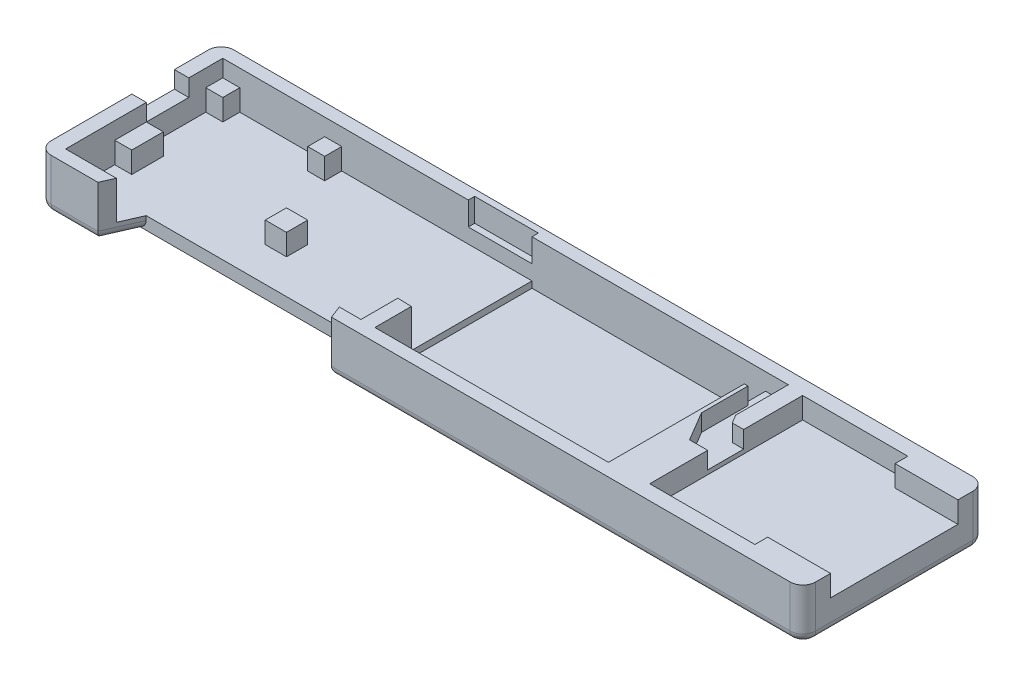
SolidWorks part; units mm, degrees
ref_plane "前视基准面" through (0, 0, 0) normal (0, 0, 1) x (1, 0, 0)
ref_plane "上视基准面" through (0, 0, 0) normal (0, 1, 0) x (1, 0, 0)
ref_plane "右视基准面" through (0, 0, 0) normal (1, 0, 0) x (0, 0, -1)
sketch "草图3" plane through (0, 0, 0) normal (0, 1, 0) x (1, 0, 0)
  line L1 (-39.9314, 29.2531) -> (140.0686, 29.2531)
  line L2 (-39.9314, 29.2531) -> (-39.9314, -13.7469)
  line L3 (-39.9314, -13.7469) -> (140.0686, -13.7469)
  line L4 (140.0686, 29.2531) -> (140.0686, -13.7469)
extrude "凸台-拉伸1" add sketch "草图3" along normal blind 12
sketch "草图4" plane through (0, 0, 0) normal (0, 1, 0) x (1, 0, 0)
  line L0 (-22.4696, -5.8589) -> (26.0023, -5.8589)
  line L1 (-39.9314, -13.7469) -> (140.0686, -13.7469) construction
  line L2 (-25.9314, -13.7469) -> (29.0686, -13.7469)
  line L5 (-25.9314, -13.7469) -> (-22.4696, -5.8589)
  line L6 (29.0686, -13.7469) -> (26.0023, -5.8589)
  point P11 (-22.4696, -5.8589)
  point P12 (26.0023, -5.8589)
extrude "切除-拉伸1" cut sketch "草图4" along normal blind 52
sketch "草图5" plane through (0, 12, 0) normal (0, 1, 0) x (1, 0, 0)
  line L6 (140.0686, -13.7469) -> (140.0686, 29.2531) construction
  line L7 (140.0686, 7.7531) -> (140.0686, 22.7531)
  line L8 (140.0686, 7.7531) -> (140.0686, -7.2469)
  line L9 (140.0686, 22.7531) -> (125.2765, 22.7531)
  line L10 (125.2765, 22.7531) -> (125.2765, -7.2469)
  line L11 (125.2765, -7.2469) -> (140.0686, -7.2469)
  point P0 (140.0686, 7.7531)
extrude "切除-拉伸2" cut sketch "草图5" against normal blind 5
sketch "草图7" plane through (0, 12, 0) normal (0, 1, 0) x (1, 0, 0)
  line L0 (125.2765, 22.7531) -> (125.2765, -7.2469) construction
  line L1 (125.2765, 7.7531) -> (125.2765, 25.7531)
  line L2 (125.2765, 7.7531) -> (125.2765, -10.2469)
  line L3 (125.2765, -10.2469) -> (100.5008, -10.2469)
  line L4 (100.5008, -10.2469) -> (100.5008, 25.7531)
  line L5 (100.5008, 25.7531) -> (125.2765, 25.7531)
  point P0 (125.2765, 7.7531)
extrude "切除-拉伸3" cut sketch "草图7" against normal blind 5
sketch "草图8" plane through (0, 12, 0) normal (0, 1, 0) x (1, 0, 0)
  line L1 (36.2763, 26.2531) -> (91.2763, 26.2531)
  line L2 (36.2763, 26.2531) -> (36.2763, -10.7469)
  line L3 (36.2763, -10.7469) -> (91.2763, -10.7469)
  line L4 (91.2763, 26.2531) -> (91.2763, -10.7469)
  line L6 (140.0686, 29.2531) -> (-39.9314, 29.2531) construction
  line L7 (29.0686, -13.7469) -> (140.0686, -13.7469) construction
  dimension "D1" = 3
  dimension "D2" = 3
extrude "切除-拉伸4" cut sketch "草图8" against normal blind 10.5
sketch "草图9" plane through (0, 12, 0) normal (0, 1, 0) x (1, 0, 0)
  line L0 (91.2763, -10.7469) -> (91.2763, 26.2531) construction
  line L1 (91.2763, 26.2531) -> (96.6358, 26.2531)
  line L2 (91.2763, 26.2531) -> (91.2763, 21.2551)
  line L4 (96.6358, 26.2531) -> (96.6358, 22.1306)
  line L5 (100.5008, 25.7531) -> (100.5008, -10.2469) construction
  line L7 (92.1327, 21.2551) -> (92.1327, 10.3104)
  line L12 (96.2367, 3.394) -> (100.5008, 3.394)
  line L13 (100.5008, 11.8772) -> (100.5008, 3.394)
  line L14 (92.1327, 10.3104) -> (96.2367, 3.394)
  line L15 (96.6358, 13.8621) -> (97.8136, 11.8772)
  line L17 (97.8136, 11.8772) -> (100.5008, 11.8772)
  line L19 (96.6358, 13.8621) -> (96.6358, 22.1306)
  line L20 (92.1327, 21.2551) -> (91.2763, 21.2551)
extrude "切除-拉伸5" cut sketch "草图9" against normal blind 4
sketch "草图10" plane through (0, 12, 0) normal (0, 1, 0) x (1, 0, 0)
  line L4 (-29.1302, -10.7469) -> (32.9986, -10.7469)
  line L5 (-29.1302, -10.7469) -> (-29.1302, -2.0631)
  line L6 (-29.1302, -2.0631) -> (32.9986, -2.0631)
  line L7 (32.9986, -10.7469) -> (32.9986, -2.0631)
extrude "切除-拉伸6" cut sketch "草图10" against normal blind 8
sketch "草图11" plane through (0, 12, 0) normal (0, 1, 0) x (1, 0, 0)
  line L0 (32.9986, -10.7469) -> (-36.5397, -10.7469)
  line L1 (36.2763, 26.2531) -> (36.2763, -10.7469) construction
  line L5 (-36.5397, 26.2531) -> (-36.5397, -10.7469)
  line L9 (36.2763, 26.2531) -> (36.2763, -2.1672)
  line L10 (-36.5397, 26.2531) -> (36.2763, 26.2531)
  line L11 (32.9986, -10.7469) -> (32.9986, -2.0631)
  line L12 (32.9986, -10.7469) -> (32.9986, -2.0631) construction
  line L13 (32.9986, -2.0631) -> (36.2763, -2.1672)
extrude "切除-拉伸8" cut sketch "草图11" against normal blind 9
fillet "圆角2" radius 2 7 edges at (140.0686, 0, -7.7531) (84.5686, 0, 13.7469) (27.5354, 0, 9.8029) (-24.2005, 0, 9.8029) (-32.9314, 0, 13.7469) (-39.9314, 0, -7.7531) (50.0686, 0, -29.2531)
fillet "圆角3" radius 3 8 edges at (-39.3456, 0.5858, -28.6673) (-39.3456, 0.5858, 13.1611) (139.4828, 0.5858, 13.1611) (139.4828, 0.5858, -28.6673) (140.0686, 7, -29.2531) (140.0686, 7, 13.7469) (-39.9314, 7, 13.7469) (-39.9314, 7, -29.2531)
sketch "草图12" plane through (-36.5397, 0, 0) normal (1, 0, 0) x (0, 0, -1)
  line L5 (8.2531, 12) -> (18.2531, 12)
  line L6 (8.2531, 12) -> (8.2531, 8)
  line L7 (8.2531, 8) -> (18.2531, 8)
  line L8 (18.2531, 12) -> (18.2531, 8)
  line L9 (26.2531, 3) -> (26.2531, 12) construction
  dimension "D1" = 10
  dimension "D2" = 8
  dimension "D3" = 4
extrude "切除-拉伸9" cut sketch "草图12" against normal blind 10
sketch "草图13" plane through (0, 3, 0) normal (0, 1, 0) x (1, 0, 0)
  line L0 (-36.5397, 26.2531) -> (-36.5397, -10.7469) construction
  line L1 (-36.5397, 22.2531) -> (-32.5397, 22.2531)
  line L2 (-36.5397, 22.2531) -> (-36.5397, 26.2531)
  line L3 (-36.5397, 26.2531) -> (-32.5397, 26.2531)
  line L4 (-32.5397, 22.2531) -> (-32.5397, 26.2531)
  line L5 (36.2763, 26.2531) -> (-36.5397, 26.2531) construction
  line L7 (-36.5397, 8.2531) -> (-32.5397, 8.2531)
  line L8 (-36.5397, 8.2531) -> (-36.5397, 0.8178)
  line L9 (-36.5397, 0.8178) -> (-32.5397, 0.8178)
  line L10 (-32.5397, 8.2531) -> (-32.5397, 0.8178)
  line L11 (-12.5397, 26.2531) -> (-8.5397, 26.2531)
  line L12 (-12.5397, 26.2531) -> (-12.5397, 22.2531)
  line L13 (-12.5397, 22.2531) -> (-8.5397, 22.2531)
  line L14 (-8.5397, 26.2531) -> (-8.5397, 22.2531)
  line L15 (-36.5397, 8.2531) -> (-36.5397, -10.7469) construction
  line L16 (-2.5397, 7.2531) -> (2.4603, 7.2531)
  line L17 (-2.5397, 7.2531) -> (-2.5397, 2.2531)
  line L18 (-2.5397, 2.2531) -> (2.4603, 2.2531)
  line L19 (2.4603, 7.2531) -> (2.4603, 2.2531)
  line L20 (96.6358, 26.2531) -> (-36.5397, 26.2531) construction
  point P16 (-12.5397, 24.2531)
  point P25 (-32.5397, 0.8178)
  dimension "D1" = 14
  dimension "D2" = 4
  dimension "D3" = 4
  dimension "D4" = 4
  dimension "D5" = 24
  dimension "D6" = 4
  dimension "D7" = 4
  dimension "D8" = 34
  dimension "D9" = 5
  dimension "D10" = 5
  dimension "D11" = 19
extrude "凸台-拉伸2" add sketch "草图13" along normal blind 5
sketch "草图14" plane through (0, 12, 0) normal (0, 1, 0) x (1, 0, 0)
  line L0 (96.6358, 26.2531) -> (-36.5397, 26.2531) construction
  line L1 (36.2763, 26.2531) -> (21.2763, 26.2531)
  line L2 (36.2763, 26.2531) -> (36.2763, 27.7531)
  line L3 (36.2763, 27.7531) -> (21.2763, 27.7531)
  line L4 (21.2763, 26.2531) -> (21.2763, 27.7531)
  line L5 (91.2763, 26.2531) -> (36.2763, 26.2531) construction
  point P8 (0, 0)
  point P9 (21.2763, 27.5966)
  dimension "D1" = 15
extrude "切除-拉伸10" cut sketch "草图14" against normal blind 5.5
